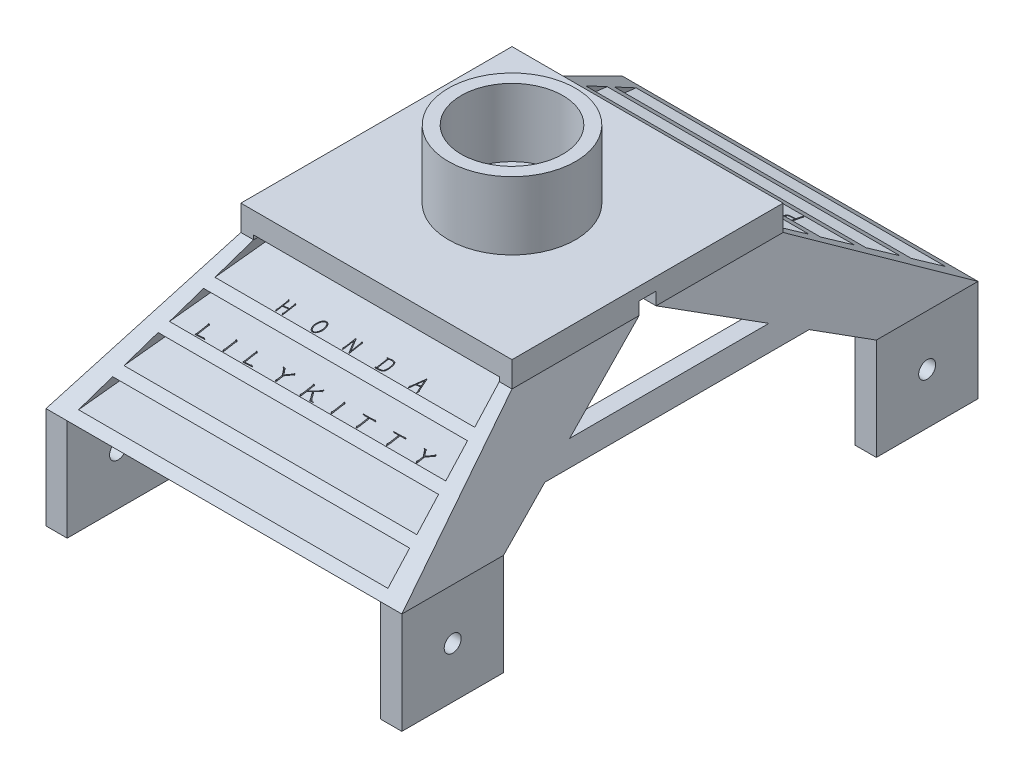
SolidWorks part; units mm, degrees
material "ABS"
ref_plane "前视基准面" through (0, 0, 0) normal (0, 0, 1) x (1, 0, 0)
ref_plane "上视基准面" through (0, 0, 0) normal (0, 1, 0) x (1, 0, 0)
ref_plane "右视基准面" through (0, 0, 0) normal (1, 0, 0) x (0, 0, -1)
other "Configuration Table"
sketch "Sketch4" plane through (0, 0, 0) normal (0, 1, 0) x (1, 0, 0)
  line L0 (0, 0) -> (2.5882, 9.6593) construction
  line L1 (32, -32) -> (-32, -32)
  line L2 (32, -32) -> (32, 32)
  line L3 (32, 32) -> (-32, 32)
  line L4 (-32, -32) -> (-32, 32)
  line L5 (32, -32) -> (-32, 32) construction
  line L6 (32, 32) -> (-32, -32) construction
  line L7 (-2.5882, 9.6593) -> (-2.2, 8.2104)
  line L8 (2.5882, 9.6593) -> (2.2, 8.2104)
  line L9 (-32, 0) -> (32, 0) construction
  line L10 (-2.5882, -9.6593) -> (-2.2, -8.2104)
  line L11 (2.5882, -9.6593) -> (2.2, -8.2104)
  circle A0 centre (0, 0) radius 2.5
  arc A1 (2.5882, 9.6593) -> (-2.5882, 9.6593) centre (0, 0) ccw
  arc A2 (2.2, 8.2104) -> (-2.2, 8.2104) centre (0, 0) ccw
  arc A3 (2.5882, -9.6593) -> (-2.5882, -9.6593) centre (0, 0) cw
  arc A4 (2.2, -8.2104) -> (-2.2, -8.2104) centre (0, 0) cw
  point P0 (0, 0)
  dimension "D3" = 30
  dimension "D1" = 64
  dimension "D2" = 64
extrude "Boss-Extrude3" add sketch "Sketch4" along normal blind 3
sketch "Sketch6" plane through (0, 3, 0) normal (0, 1, 0) x (1, 0, 0)
  circle A0 centre (0, 0) radius 15
  circle A1 centre (0, 0) radius 12
extrude "Boss-Extrude4" add sketch "Sketch6" along normal blind 16
ref_plane "Plane1" through (0, -50, 0) normal (0, 1, 0) x (1, 0, 0)
sketch "Sketch8" plane through (0, -50, 0) normal (0, 1, 0) x (1, 0, 0)
  line L0 (0, -32) -> (0, 32) construction
  line L3 (-32, 0) -> (32, 0) construction
  line L7 (37, -68) -> (42, -68)
  line L8 (37, -68) -> (37, -44)
  line L9 (37, -44) -> (42, -44)
  line L10 (42, -68) -> (42, -44)
  line L18 (-37, -44) -> (-42, -44)
  line L19 (-42, -68) -> (-42, -44)
  line L20 (-37, -68) -> (-42, -68)
  line L21 (-37, -68) -> (-37, -44)
  line L22 (37, 44) -> (42, 44)
  line L23 (42, 68) -> (42, 44)
  line L24 (37, 68) -> (42, 68)
  line L25 (37, 68) -> (37, 44)
  line L26 (-37, 68) -> (-37, 44)
  line L27 (-37, 68) -> (-42, 68)
  line L28 (-42, 68) -> (-42, 44)
  line L29 (-37, 44) -> (-42, 44)
  dimension "D1" = 5
  dimension "D2" = 37
  dimension "D3" = 24
  dimension "D4" = 44
sketch "Sketch12" plane through (0, 0, 0) normal (0, -1, 0) x (1, 0, 0)
  line L0 (-32, 0) -> (32, 0) construction
  line L1 (32, 32) -> (29, 32)
  line L2 (32, 32) -> (32, 2)
  line L3 (32, 2) -> (29, 2)
  line L4 (29, 32) -> (29, 2)
  line L5 (-32, -32) -> (-32, 32) construction
  line L6 (32, 32) -> (32, -32) construction
  line L7 (0, 32) -> (0, -32) construction
  line L8 (-32, 32) -> (32, 32) construction
  line L9 (32, -32) -> (-32, -32) construction
  line L10 (32, -2) -> (29, -2)
  line L11 (29, -32) -> (29, -2)
  line L12 (32, -32) -> (29, -32)
  line L13 (32, -32) -> (32, -2)
  line L14 (-32, 2) -> (-29, 2)
  line L15 (-29, 32) -> (-29, 2)
  line L16 (-32, 32) -> (-29, 32)
  line L17 (-32, 32) -> (-32, 2)
  line L18 (-32, -32) -> (-32, -2)
  line L19 (-32, -32) -> (-29, -32)
  line L20 (-29, -32) -> (-29, -2)
  line L21 (-32, -2) -> (-29, -2)
  dimension "D1" = 3
  dimension "D2" = 30
extrude "Boss-Extrude7" add sketch "Sketch8" along normal blind 24 separate body
sketch "Sketch16" plane through (0, 0, 0) normal (1, 0, 0) x (0, 0, -1)
  line L0 (-68, -26) -> (-68, -50) construction
  line L1 (68, -26) -> (68, -50) construction
  circle A0 centre (-56, -38) radius 2
  circle A1 centre (56, -38) radius 2
  dimension "D1" = 12
  dimension "D2" = 12
extrude "Cut-Extrude3" cut sketch "Sketch16" against normal blind 85
extrude "Cut-Extrude4" cut sketch "Sketch16<2>" along normal blind 114
sketch "Sketch16<2>" plane through (0, 0, 0) normal (1, 0, 0) x (0, 0, -1) same geometry as "Sketch16"
extrude "Boss-Extrude8" add sketch "Sketch12" along normal blind 3
loft "Loft4" add section face at (-30.5, -3, -17) section face at (-39.5, -26, -56) connector at (-29, -3, -32) connector at (-37, -26, -68)
loft "Loft5" add section face at (-30.5, -3, 17) section face at (-39.5, -26, 56) connector at (-32, -3, 32) connector at (-42, -26, 68)
loft "Loft6" add section face at (30.5, -3, -17) section face at (39.5, -26, -56) connector at (32, -3, -32) connector at (42, -26, -68)
loft "Loft7" add section face at (30.5, -3, 17) section face at (39.5, -26, 56) connector at (29, -3, 32) connector at (37, -26, 68)
sketch "Sketch23" plane through (0, 0, 0) normal (0, -1, 0) x (1, 0, 0)
  line L0 (29, 32) -> (29, 2) construction
  line L1 (-29, 32) -> (29, 32)
  line L2 (-29, 32) -> (-29, 30)
  line L3 (-29, 30) -> (29, 30)
  line L4 (29, 32) -> (29, 30)
  line L5 (-32, 0) -> (32, 0) construction
  line L6 (-32, -2) -> (-32, 2) construction
  line L7 (32, 2) -> (32, -2) construction
  line L8 (-29, 2) -> (-29, 32) construction
  line L9 (-29, 22) -> (29, 22)
  line L10 (-29, 22) -> (-29, 20)
  line L11 (-29, 20) -> (29, 20)
  line L12 (29, 22) -> (29, 20)
  line L13 (-29, -10) -> (29, -10)
  line L14 (-29, 12) -> (29, 12)
  line L15 (-29, 12) -> (-29, 10)
  line L16 (-29, 10) -> (29, 10)
  line L17 (29, 12) -> (29, 10)
  line L18 (29, -12) -> (29, -10)
  line L19 (-29, -12) -> (29, -12)
  line L20 (-29, -12) -> (-29, -10)
  line L21 (-29, -20) -> (29, -20)
  line L22 (29, -22) -> (29, -20)
  line L23 (-29, -22) -> (29, -22)
  line L24 (-29, -22) -> (-29, -20)
  line L25 (-29, -30) -> (29, -30)
  line L26 (29, -32) -> (29, -30)
  line L27 (-29, -32) -> (29, -32)
  line L28 (-29, -32) -> (-29, -30)
  dimension "D1" = 2
  dimension "D2" = 2
  dimension "D3" = 8
  dimension "D4" = 2
  dimension "D5" = 8
extrude "Boss-Extrude14" add sketch "Sketch23" along normal blind 2
sketch "Sketch30" plane through (0, 0, 0) normal (1, 0, 0) x (0, 0, -1)
  line L0 (-17, -3) -> (-56, -26) construction
  line L1 (-2, -3) -> (-32, -3) construction
  line L2 (-68, -26) -> (-44, -26) construction
  line L3 (-68, -26) -> (-50.8819, -22.9816)
  line L4 (-65.8048, -24.5975) -> (-48.4257, -21.5331)
  line L5 (-32, -3) -> (-68, -26) construction
  line L6 (-41.0571, -17.1875) -> (-59.2191, -20.39)
  line L7 (-38.6009, -15.739) -> (-57.0239, -18.9875)
  line L8 (-31.2324, -11.3935) -> (-50.4382, -14.78)
  line L9 (-28.7762, -9.9449) -> (-48.243, -13.3775)
  line L10 (-21.4077, -5.5994) -> (-41.6573, -9.17)
  line L11 (-18.9515, -4.1509) -> (-39.4621, -7.7675)
  line L12 (-65.8048, -24.5975) -> (-68, -26)
  line L13 (-48.4257, -21.5331) -> (-50.8819, -22.9816)
  line L14 (-18.9515, -4.1509) -> (-21.4077, -5.5994)
  line L15 (-39.4621, -7.7675) -> (-41.6573, -9.17)
  line L16 (-48.243, -13.3775) -> (-50.4382, -14.78)
  line L17 (-57.0239, -18.9875) -> (-59.2191, -20.39)
  line L18 (-38.6009, -15.739) -> (-41.0571, -17.1875)
  line L19 (-28.7762, -9.9449) -> (-31.2324, -11.3935)
  dimension "D1" = 10
  dimension "D2" = 1
  dimension "D3" = 3
  dimension "D4" = 1
  dimension "D5" = 3
  dimension "D6" = 1
  dimension "D7" = 3
  dimension "D8" = 1
extrude "Boss-Extrude19" add sketch "Sketch30" along normal blind 45 and the other way blind 47
sketch "Sketch31" plane through (0, 0, 0) normal (0, 0, 1) x (1, 0, 0)
  line L0 (-32, -3) -> (-42, -26)
  line L1 (-42, -26) -> (-54.1068, -26)
  line L2 (-54.1068, -26) -> (-54.1068, -3)
  line L3 (-54.1068, -3) -> (-32, -3)
  line L4 (32, -3) -> (50.2676, -3)
  line L5 (50.2676, -3) -> (50.2676, -26)
  line L6 (50.2676, -26) -> (42, -26)
  line L7 (42, -26) -> (32, -3)
extrude "Cut-Extrude9" cut sketch "Sketch31" along normal blind 95
mirror "Mirror7" about plane through (0, 0, 0) normal (0, 0, 1) of "Cut-Extrude9", "Boss-Extrude19"
sketch "Sketch32" plane through (0, 0, 0) normal (0, 0, 1) x (1, 0, 0)
  line L22 (34.5609, -18.9875) -> (38.9511, -18.9875)
  line L23 (-34.5609, -18.9875) -> (34.5609, -18.9875) construction
  line L24 (33.0974, -14.78) -> (34.5609, -18.9875) construction
  line L25 (32, -3) -> (42, -26) construction
  line L26 (34.5609, -18.9875) -> (33.0974, -14.78)
  line L27 (33.0974, -14.78) -> (37.1217, -14.78)
  line L28 (37.1217, -14.78) -> (38.9511, -18.9875)
extrude "Boss-Extrude21" add sketch "Sketch32" along normal blind 44 and the other way blind 37
mirror "Mirror8" about plane through (0, 0, 0) normal (1, 0, 0) of "Boss-Extrude21"
ref_plane "Plane2" through (0, -15, 0) normal (0, 1, 0) x (1, 0, 0)
sketch "Sketch34" plane through (0, -15, 0) normal (0, 1, 0) x (1, 0, 0)
  line L0 (-32, 0) -> (49968, 0) construction
  line L3 (-32, 2) -> (-32, -2) construction
  line L8 (32, -2) -> (32, 2) construction
  line L10 (-9, -10) -> (-5, -10)
  line L11 (-9, -10) -> (-9, 10)
  line L12 (-9, 10) -> (-5, 10)
  line L13 (-5, -10) -> (-5, 10)
  line L14 (-9, -10) -> (-5, 10) construction
  line L15 (-9, 10) -> (-5, -10) construction
  point P4 (-32, 0)
  point P7 (32, 0)
  point P8 (-7, 0)
  point P14 (-5, 0)
  dimension "D1" = 5
  dimension "D2" = 4
  dimension "D3" = 20
extrude "Boss-Extrude23" add sketch "Sketch34" against normal blind 25
extrude "Boss-Extrude24" add sketch "Sketch34<2>" along normal blind 17 and the other way blind 30
sketch "Sketch34<2>" plane through (0, -15, 0) normal (0, 1, 0) x (1, 0, 0) same geometry as "Sketch34"
sketch "Sketch35" plane through (0, -0.7848, -0.1384) normal (0, 0.9848, 0.1736) x (1, 0, 0)
  text T0 "HONDA" font "汉仪长仿宋体" height 3.5
extrude "Cut-Extrude10" cut sketch "Sketch35" against normal blind 1
sketch "Sketch36" plane through (0, -4.724, -0.833) normal (0, 0.9848, 0.1736) x (1, 0, 0)
  text T0 "LILYKITTY" font "汉仪长仿宋体" height 3.5
extrude "Cut-Extrude11" cut sketch "Sketch36" against normal blind 1
sketch "Sketch38" plane through (0, -0.7848, 0.1384) normal (0, 0.9848, -0.1736) x (1, 0, 0)
  text T0 "PiSQUAD" font "汉仪长仿宋体" height 3.5
extrude "Cut-Extrude12" cut sketch "Sketch38" against normal blind 1
sketch "Sketch39" plane through (0, -4.724, 0.833) normal (0, 0.9848, -0.1736) x (1, 0, 0)
  text T0 "PIONEER" font "汉仪长仿宋体" height 3.5
extrude "Cut-Extrude13" cut sketch "Sketch39" against normal blind 1
